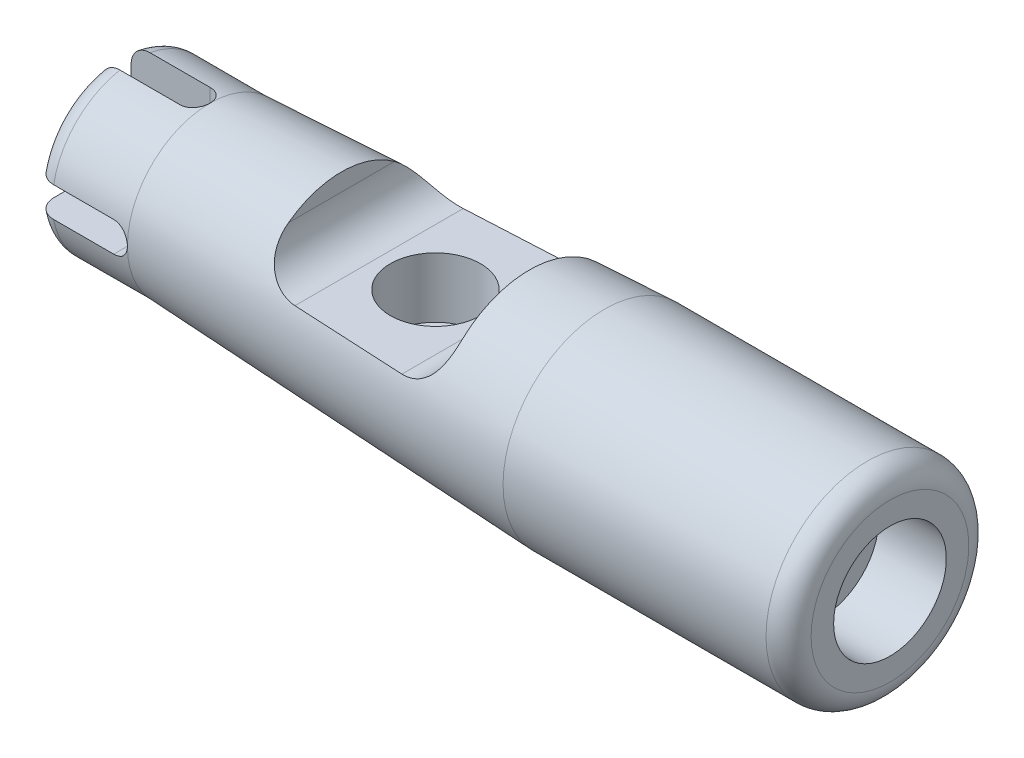
SolidWorks part; units mm, degrees
ref_plane "前基準面" through (0, 0, 0) normal (0, 0, 1) x (1, 0, 0)
ref_plane "上基準面" through (0, 0, 0) normal (0, 1, 0) x (1, 0, 0)
ref_plane "右基準面" through (0, 0, 0) normal (1, 0, 0) x (0, 0, -1)
sketch "草圖1" plane through (0, 0, 0) normal (0, 0, 1) x (1, 0, 0)
  line L0 (-42.6735, 0) -> (45.9536, 0) construction
  line L1 (92.0296, 27) -> (-12.9704, 22)
  line L2 (-37.9704, 0) -> (-12.9704, 0)
  line L3 (-37.9704, 0) -> (-37.9704, 22)
  line L4 (-37.9704, 22) -> (-12.9704, 22)
  line L6 (92.0296, 0) -> (168.0296, 0)
  line L8 (92.0296, 27) -> (168.0296, 27)
  line L9 (168.0296, 0) -> (168.0296, 27)
  line L10 (-12.9704, 0) -> (92.0296, 0)
  dimension "D1" = 22
  dimension "D2" = 25
  dimension "D3" = 76
  dimension "D4" = 27
  dimension "D5" = 105
revolve "旋轉1" add sketch "草圖1" angle 360 about L0
sketch "草圖2" plane through (0, 0, 0) normal (0, 0, 1) x (1, 0, 0)
  line L0 (-60.4904, 0) -> (-37.9704, 0) construction
  line L7 (-37.9704, 22) -> (-37.9704, -22) construction
  line L11 (-37.9704, -4) -> (-37.9704, 4)
  line L12 (-37.9704, 4) -> (-16.9704, 4)
  line L14 (-16.9704, 0) -> (10.2478, 0) construction
  line L15 (-37.9704, -4) -> (-16.9704, -4)
  arc A1 (-16.9704, 4) -> (-16.9704, -4) centre (-16.9704, 0) cw
  dimension "D1" = 4
  dimension "D2" = 21
extrude "除料-伸長1" cut sketch "草圖2" against normal through all
pattern_circular "環狀複製排列1" count 4 over 360 about axis through (-37.9704, 0, 0) along (-1, 0, 0) of "除料-伸長1"
sketch "草圖4" plane through (0, 0, 0) normal (0, 0, 1) x (1, 0, 0)
  line L0 (22.0296, 23.6667) -> (22.0296, 9)
  line L2 (92.0296, 27) -> (-12.9704, 22) construction
  line L3 (22.0296, 9) -> (72.0296, 9)
  line L7 (72.0296, 9) -> (72.0296, 26.0476)
  line L8 (92.0296, 27) -> (92.0296, -27) construction
  line L9 (168.0296, 27) -> (92.0296, 27) construction
  line L10 (22.0296, 23.6667) -> (72.0296, 26.0476)
  dimension "D1" = 50
  dimension "D2" = 20
  dimension "D3" = 18
extrude "除料-伸長2" cut sketch "草圖4" against normal through all both and the other way through all
sketch "草圖5" plane through (0, 9, 0) normal (0, 1, 0) x (1, 0, 0)
  line L0 (72.0296, 24.4434) -> (72.0296, -24.4434) construction
  circle A0 centre (47.0296, 0) radius 12
  dimension "D1" = 24
  dimension "D2" = 25
extrude "除料-伸長3" cut sketch "草圖5" against normal blind 16
sketch "草圖6" plane through (0, 0, 0) normal (0, 0, 1) x (1, 0, 0)
  line L1 (92.0296, -27) -> (152.0296, -27)
  line L2 (92.0296, -27) -> (92.0296, -22)
  line L3 (92.0296, -22) -> (152.0296, -22)
  line L4 (152.0296, -27) -> (152.0296, -22)
  dimension "D1" = 60
  dimension "D2" = 5
extrude "除料-伸長4" cut sketch "草圖6" against normal through all both and the other way through all
sketch "草圖7" plane through (0, -22, 0) normal (0, -1, 0) x (1, 0, 0)
  line L2 (168.0296, -27) -> (168.0296, 27) construction
  line L3 (82.7398, 0) -> (178.2064, 0) construction
  circle A0 centre (122.0296, 12) radius 3
  circle A1 centre (122.0296, -12) radius 3
  dimension "D1" = 6
  dimension "D2" = 46
  dimension "D3" = 12
  dimension "D4" = 12
extrude "除料-伸長5" cut sketch "草圖7" against normal blind 12
sketch "草圖8" plane through (0, 0, 0) normal (0, 0, 1) x (1, 0, 0)
  line L0 (-54.5608, 0) -> (179.9126, 0) construction
  line L1 (168.0296, -27) -> (168.0296, 27) construction
  line L2 (168.0296, 0) -> (150.0296, 0)
  line L3 (168.0296, 0) -> (168.0296, 15)
  line L4 (168.0296, 15) -> (150.0296, 15)
  line L6 (130.0296, 6) -> (119.6373, 0)
  line L8 (150.0296, 6) -> (150.0296, 15)
  line L11 (150.0296, 0) -> (130.0296, 0)
  line L13 (150.0296, 6) -> (130.0296, 6)
  line L15 (119.6373, 0) -> (130.0296, 0)
  dimension "D1" = 15
  dimension "D2" = 18
  dimension "D3" = 38
  dimension "D4" = 6
  dimension "D5" = 150
  dimension "D6" = 6
revolve "除料-旋轉1" cut sketch "草圖8" angle 360 about L0
fillet "圓角1" radius 10 2 edges at (22.0296, 9, 0) (72.0296, 9, 0)
fillet "圓角2" radius 6 1 edges at (168.0296, 0, 27)
fillet "圓角3" radius 5 4 edges at (-37.9704, 15.5563, 15.5563) (-37.9704, -15.5563, 15.5563) (-37.9704, -15.5563, -15.5563) (-37.9704, 15.5563, -15.5563)
fillet "圓角4" radius 5 2 edges at (152.0296, -22, 0) (92.0296, -22, 0)
